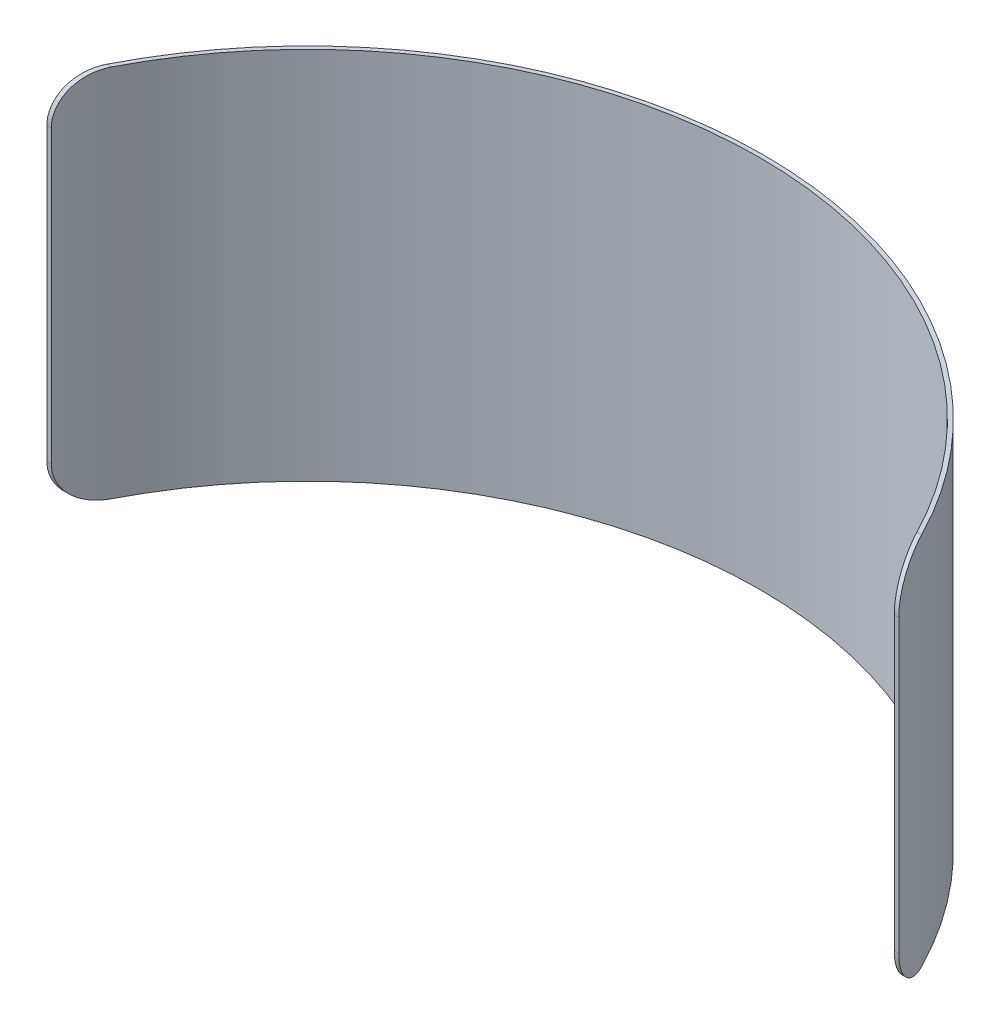
SolidWorks part; units mm, degrees
ref_plane "Front Plane" through (0, 0, 0) normal (0, 0, 1) x (1, 0, 0)
ref_plane "Top Plane" through (0, 0, 0) normal (0, 1, 0) x (1, 0, 0)
ref_plane "Right Plane" through (0, 0, 0) normal (1, 0, 0) x (0, 0, -1)
sketch "Sketch1" plane through (0, 0, 0) normal (0, 1, 0) x (1, 0, 0)
  line L0 (0, 0) -> (10.7392, 0)
  line L1 (2050, 0) -> (2039.2608, 0)
  arc A0 (0, 0) -> (2050, 0) centre (1025, -399.218) cw
  arc A1 (10.7392, 0) -> (2039.2608, 0) centre (1025, -399.218) cw
  arc A2 (9.3182, -3.6293) -> (2040.6818, -3.6293) centre (1025, -399.218) cw construction
  dimension "D2" = 1100
  dimension "D1" = 2050
  dimension "D3" = 10
extrude "Boss-Extrude1" add sketch "Sketch1" along normal blind 900
fillet "Fillet1" radius 100 4 edges at (2044.6304, 900, 0) (2044.6304, 0, 0) (5.3696, 0, 0) (5.3696, 900, 0)
